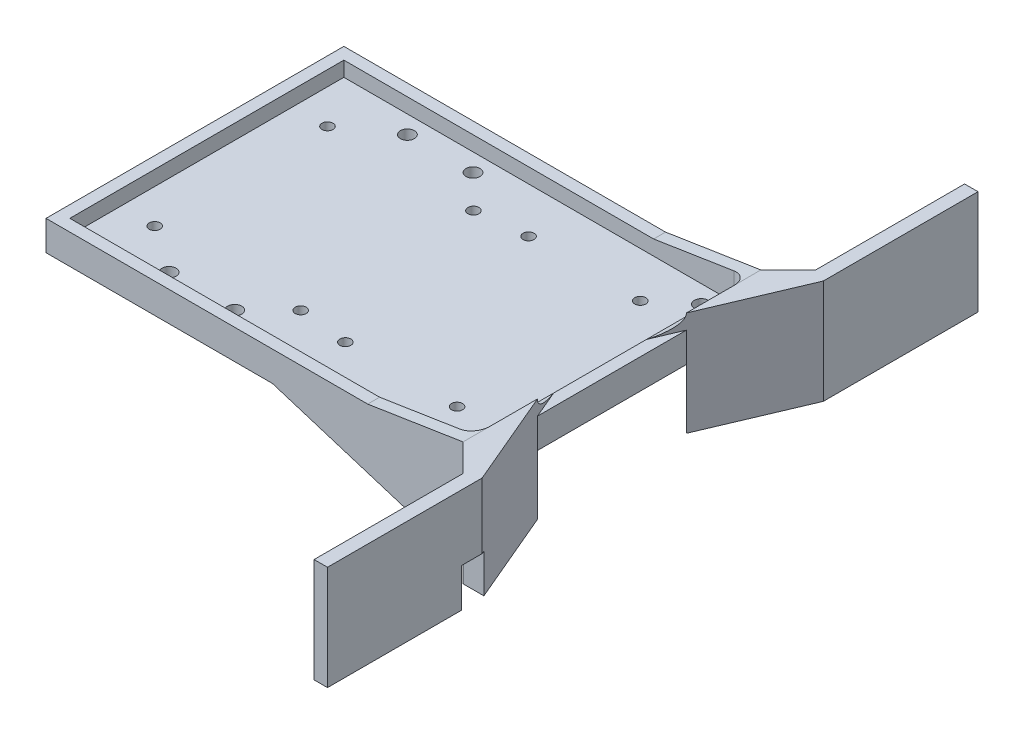
SolidWorks part; units mm, degrees
material "ABS"
ref_plane "前视基准面" through (0, 0, 0) normal (0, 0, 1) x (1, 0, 0)
ref_plane "上视基准面" through (0, 0, 0) normal (0, 1, 0) x (1, 0, 0)
ref_plane "右视基准面" through (0, 0, 0) normal (1, 0, 0) x (0, 0, -1)
sketch "Sketch1" plane through (0, 0, 0) normal (0, 1, 0) x (1, 0, 0)
  line L1 (-70, 50) -> (70, 50)
  line L2 (-70, 50) -> (-70, -50)
  line L3 (-70, -50) -> (70, -50)
  line L4 (70, 50) -> (70, -50)
  line L5 (0, -50) -> (0, 50) construction
  line L6 (-70, 0) -> (70, 0) construction
  point P0 (0, 0)
  dimension "D1" = 140
  dimension "D2" = 100
extrude "Boss-Extrude1" add sketch "Sketch1" along normal blind 10
sketch "Sketch2" plane through (0, 10, 0) normal (0, 1, 0) x (1, 0, 0)
  line L12 (66, -46) -> (66, 46)
  line L13 (66, 46) -> (-66, 46)
  line L14 (-66, 46) -> (-66, -46)
  line L15 (-66, -46) -> (66, -46)
  line L16 (66, -46) -> (66, 46)
  line L17 (66, 46) -> (-66, 46)
  line L18 (-66, 46) -> (-66, -46)
  line L19 (-66, -46) -> (66, -46)
  dimension "D1" = 4
extrude "Cut-Extrude1" cut sketch "Sketch2" against normal blind 5
sketch "Sketch6" plane through (0, 5, 0) normal (0, 1, 0) x (1, 0, 0)
  line L8 (-60, -40) -> (60, -40)
  line L9 (60, -40) -> (60, 40)
  line L10 (60, 40) -> (-60, 40)
  line L11 (-60, 40) -> (-60, -40)
  line L12 (-60, -40) -> (60, -40) construction
  line L13 (60, -40) -> (60, 40) construction
  line L14 (60, 40) -> (-60, 40) construction
  line L15 (-60, 40) -> (-60, -40) construction
  circle A0 centre (60, 40) radius 2.35
  circle A1 centre (60, -40) radius 2.35
  circle A2 centre (-60, -40) radius 2.35 construction
  circle A3 centre (-60, 40) radius 2.35 construction
  circle A4 centre (0, 40) radius 2.35 construction
  circle A5 centre (0, -40) radius 2.35 construction
  circle A6 centre (-16.6415, -40) radius 2.35
  circle A7 centre (-16.6415, 40) radius 2.35
  circle A8 centre (-38.6748, -40) radius 2.35
  circle A9 centre (-38.6748, 40) radius 2.35
  dimension "D2" = 4.7
  dimension "D1" = 6
extrude "Cut-Extrude2" cut sketch "Sketch6" against normal up to next
sketch "Sketch9" plane through (0, 5, 0) normal (0, 1, 0) x (1, 0, 0)
  line L0 (-60, 40) -> (0, -40) construction
  line L1 (0, -40) -> (60, 40) construction
  line L3 (-58, 32.5) -> (-2, 32.5) construction
  line L4 (-58, 32.5) -> (-58, -32.5) construction
  line L5 (-58, -32.5) -> (-2, -32.5) construction
  line L6 (-2, 32.5) -> (-2, -32.5) construction
  line L7 (-30, -32.5) -> (-30, 32.5) construction
  line L8 (-58, 0) -> (-2, 0) construction
  line L9 (7.55, 34.2) -> (52.45, 34.2) construction
  line L10 (7.55, 34.2) -> (7.55, -34.2) construction
  line L11 (7.55, -34.2) -> (52.45, -34.2) construction
  line L12 (52.45, 34.2) -> (52.45, -34.2) construction
  line L13 (30, -34.2) -> (30, 34.2) construction
  line L14 (7.55, 0) -> (52.45, 0) construction
  line L15 (-54.5, 29) -> (-5.5, 29) construction
  line L16 (-54.5, 29) -> (-54.5, -29) construction
  line L17 (-54.5, -29) -> (-5.5, -29) construction
  line L18 (-5.5, 29) -> (-5.5, -29) construction
  line L19 (-30, -29) -> (-30, 29) construction
  line L20 (-54.5, 0) -> (-5.5, 0) construction
  line L21 (11.25, 30.75) -> (48.75, 30.75) construction
  line L22 (11.25, 30.75) -> (11.25, -30.75) construction
  line L23 (11.25, -30.75) -> (48.75, -30.75) construction
  line L24 (48.75, 30.75) -> (48.75, -30.75) construction
  line L25 (30, -30.75) -> (30, 30.75) construction
  line L26 (11.25, 0) -> (48.75, 0) construction
  circle A0 centre (-54.5, 29) radius 1.85
  circle A1 centre (-5.5, 29) radius 1.85
  circle A2 centre (-54.5, -29) radius 1.85
  circle A3 centre (-5.5, -29) radius 1.85
  circle A4 centre (11.25, 30.75) radius 1.85
  circle A5 centre (48.75, 30.75) radius 1.85
  circle A6 centre (48.75, -30.75) radius 1.85
  circle A7 centre (11.25, -30.75) radius 1.85
  circle A9 centre (-60, 40) radius 2.35 construction
  circle A10 centre (0, -40) radius 2.35 construction
  point P4 (-30, 0)
  point P10 (30, 0)
  point P14 (-30, 0)
  point P18 (30, 0)
  dimension "D9" = 3.7
  dimension "D1" = 56
  dimension "D2" = 65
  dimension "D3" = 49
  dimension "D4" = 58
  dimension "D5" = 68.4
  dimension "D6" = 44.9
  dimension "D7" = 37.5
  dimension "D8" = 61.5
extrude "Cut-Extrude3" cut sketch "Sketch9" against normal up to next
sketch "Sketch11" plane through (0, 0, 0) normal (0, 1, 0) x (1, 0, 0)
  line L0 (70, 50) -> (79.1924, 59.1924)
  line L1 (70, -50) -> (70, 50) construction
  line L2 (79.1924, 59.1924) -> (79.1924, 109.1924)
  line L3 (79.1924, 109.1924) -> (83.6924, 109.1924)
  line L4 (83.6924, 109.1924) -> (83.6924, 57.2572)
  line L5 (83.6924, 57.2572) -> (70, 25)
  line L6 (70, 25) -> (70, 50)
  line L7 (-5.5, 0) -> (5.5, 0) construction
  line L8 (70, -25) -> (70, -50)
  line L9 (83.6924, -57.2572) -> (70, -25)
  line L10 (83.6924, -109.1924) -> (83.6924, -57.2572)
  line L11 (79.1924, -109.1924) -> (83.6924, -109.1924)
  line L12 (79.1924, -59.1924) -> (79.1924, -109.1924)
  line L13 (70, -50) -> (79.1924, -59.1924)
  dimension "D1" = 4.5
  dimension "D2" = 50
  dimension "D3" = 13
  dimension "D4" = 25
  dimension "D5" = 135
  dimension "D6" = 23
extrude "Boss-Extrude2" add sketch "Sketch11" against normal blind 20 and the other way blind 15
sketch "Sketch12" plane through (0, 0, -50) normal (0, 0, -1) x (-1, 0, 0)
  line L0 (-70, 15) -> (-38, 10)
  line L1 (-70, 10) -> (70, 10) construction
  line L2 (-38, 10) -> (-70, 10)
  line L3 (-70, 10) -> (-70, 15)
  line L4 (-70, -20) -> (-70, 0)
  line L5 (-70, 0) -> (-6, 0)
  line L6 (-70, 0) -> (70, 0) construction
  line L7 (-6, 0) -> (-70, -20)
  dimension "D1" = 32
  dimension "D2" = 64
extrude "Boss-Extrude3" add sketch "Sketch12" against normal blind 4
fillet "Fillet3" radius 5 1 edges at (70, 10, -35.5)
fillet "Fillet4" radius 5 1 edges at (70, 14.9495, -46)
mirror "Mirror6" about plane through (0, 0, 0) normal (0, 0, 1) of "Boss-Extrude3"
fillet "Fillet5" radius 5 1 edges at (70, 10, 35.5)
fillet "Fillet6" radius 5 1 edges at (70, 14.9495, 46)
fillet "Fillet7" radius 14 2 edges at (70, -10, 46) (70, -10, -46)
sketch "Sketch13" plane through (83.6924, 0, 0) normal (1, 0, 0) x (0, 0, -1)
  line L0 (-56.2572, -20) -> (-56.2572, -7)
  line L1 (-109.1924, -20) -> (-57.2572, -20) construction
  line L2 (-56.2572, -7) -> (-64.2572, -7)
  line L3 (-64.2572, -7) -> (-64.2572, -20)
  line L4 (-64.2572, -20) -> (-56.2572, -20)
  line L6 (-57.2572, 15) -> (-57.2572, -20) construction
  dimension "D1" = 1
  dimension "D2" = 8
  dimension "D3" = 13
extrude "Cut-Extrude4" cut sketch "Sketch13" against normal up to next
